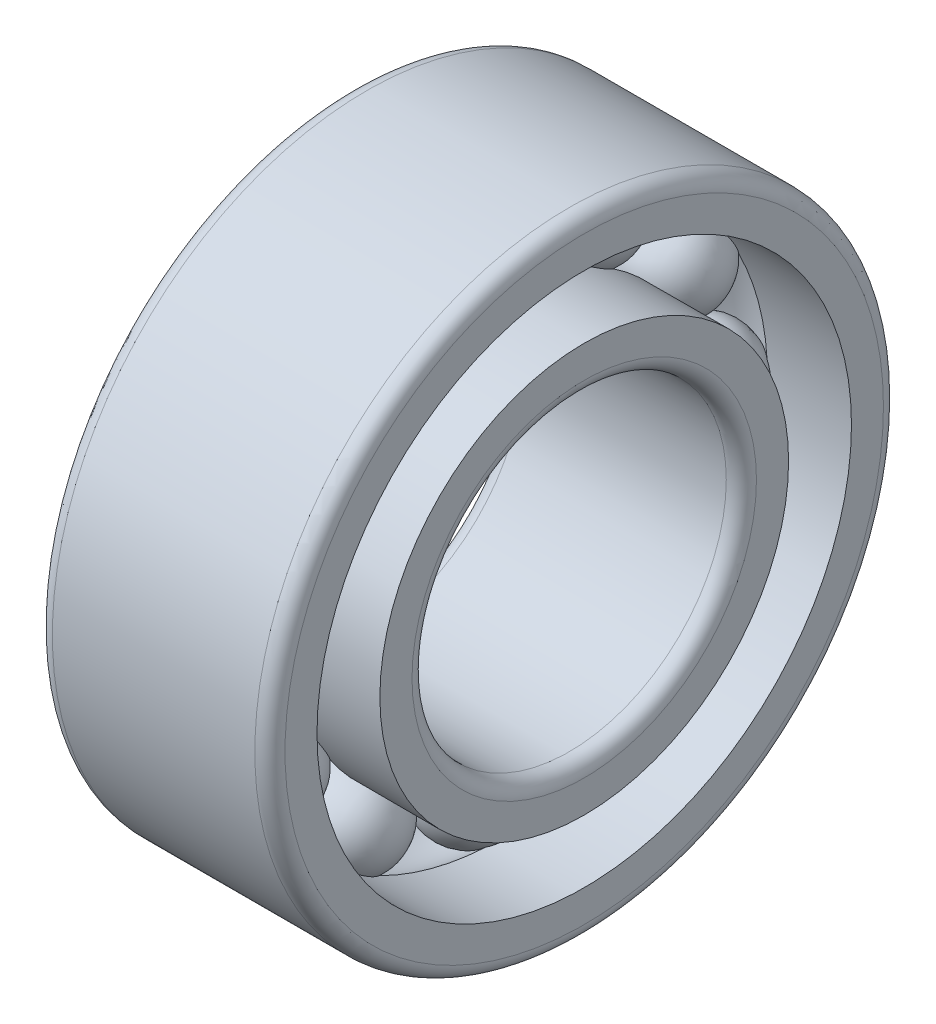
SolidWorks part; units mm, degrees
note: '?' marks a value the reader was unsure of.
ref_plane "Front" through (0, 0, 0) normal (0, 0, 1) x (1, 0, 0)
ref_plane "Top" through (0, 0, 0) normal (0, 1, 0) x (1, 0, 0)
ref_plane "Right" through (0, 0, 0) normal (1, 0, 0) x (0, 0, -1)
sketch "Sketch1" plane through (0, 0, 0) normal (0, 0, 1) x (1, 0, 0)
  line L0 (-0.6533, 5.3975) -> (-2.3495, 5.3975)
  line L1 (-2.3495, 5.3975) -> (-2.3495, 6.0433)
  line L2 (-2.0447, 6.3481) -> (2.0447, 6.3481)
  line L3 (2.3495, 6.0433) -> (2.3495, 5.3975)
  line L4 (2.3495, 5.3975) -> (0.6533, 5.3975)
  line L5 (-3.175, 0) -> (3.175, 0) construction
  arc A0 (-2.3495, 6.0433) -> (-2.0447, 6.3481) centre (-2.0447, 6.0433) cw
  arc A1 (2.0447, 6.3481) -> (2.3495, 6.0433) centre (2.0447, 6.0433) cw
  arc A2 (0.6533, 5.3975) -> (-0.6533, 5.3975) centre (0, 4.5783) ccw
  dimension "D4" = 1.0477
  dimension "D5" = 0.3048
  dimension "D1" = 10.795
  dimension "D2" = 12.6962
  dimension "D3" = 9.1567
  dimension "D6" = 4.699
revolve "Base-Revolve" add sketch "Sketch1" angle 360 about L5
ref_axis "Axis1" through (-50, 0, 0) along (1, 0, 0)?
sketch "Sketch2" plane through (0, 0, 0) normal (0, 0, 1) x (1, 0, 0)
  line L0 (-0.9525, 4.7625) -> (0.9525, 4.7625)
  line L1 (-1.905, 4.7625) -> (1.905, 4.7625) construction
  arc A0 (0.9525, 4.7625) -> (-0.9525, 4.7625) centre (0, 4.7625) cw
  dimension "D2" = 0.9525
  dimension "D1" = 4.7625
revolve "Boss-Revolve1" add sketch "Sketch2" angle 360 about L1
pattern_circular "CirPattern1" count 12 every 30 about axis through (0, 0, 0) along (1, 0, 0) of "Boss-Revolve1", "Base-Revolve"
sketch "Sketch3" plane through (0, 0, 0) normal (0, 0, 1) x (1, 0, 0)
  line L0 (-0.6533, 4.1275) -> (-2.3495, 4.1275)
  line L1 (-2.3495, 4.1275) -> (-2.3495, 3.4785)
  line L2 (-2.0447, 3.1737) -> (2.0447, 3.1737)
  line L3 (2.3495, 3.4785) -> (2.3495, 4.1275)
  line L4 (2.3495, 4.1275) -> (0.6533, 4.1275)
  line L5 (-3.175, 0) -> (3.175, 0) construction
  arc A0 (-2.3495, 3.4785) -> (-2.0447, 3.1737) centre (-2.0447, 3.4785) ccw
  arc A1 (2.0447, 3.1737) -> (2.3495, 3.4785) centre (2.0447, 3.4785) ccw
  arc A2 (0.6533, 4.1275) -> (-0.6533, 4.1275) centre (0, 4.9466) cw
  dimension "D1" = 1.0477
  dimension "D5" = 0.3048
  dimension "D2" = 6.3475
  dimension "D3" = 8.255
  dimension "D4" = 9.8933
  dimension "D6" = 4.699
revolve "Boss-Revolve2" add sketch "Sketch3" angle 360 about L5
